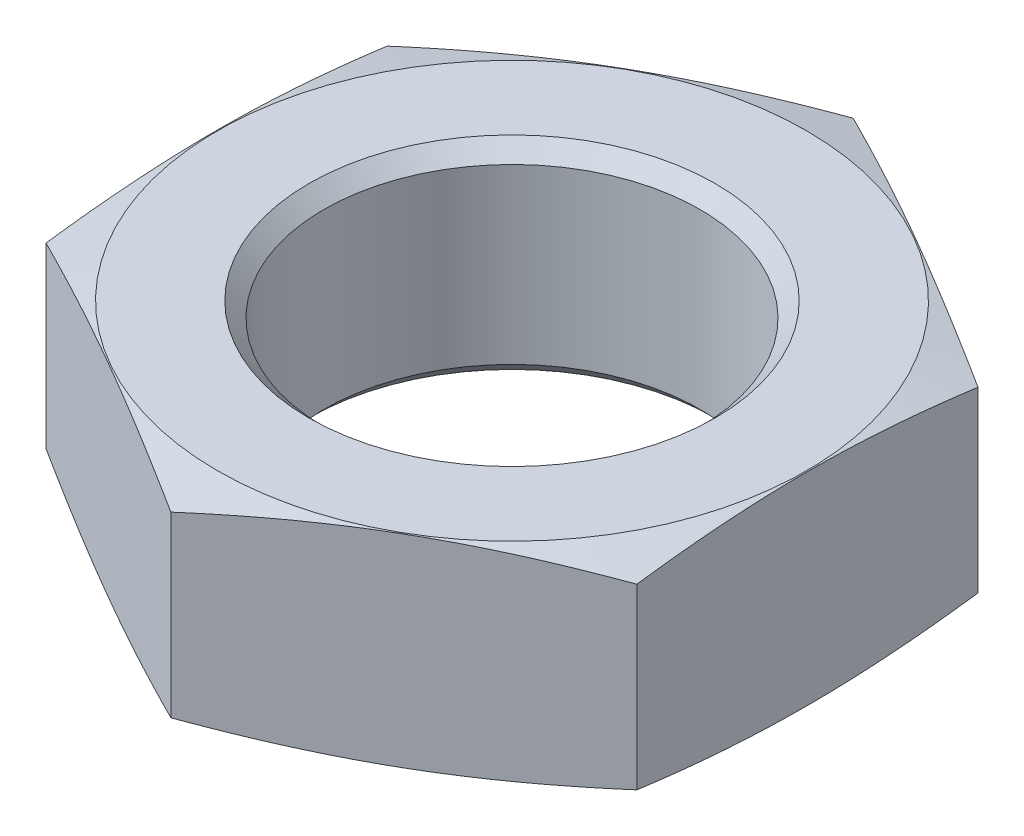
SolidWorks part; units mm, degrees
ref_plane "Ebene vorne" through (0, 0, 0) normal (0, 0, 1) x (1, 0, 0)
ref_plane "Ebene oben" through (0, 0, 0) normal (0, 1, 0) x (1, 0, 0)
ref_plane "Ebene rechts" through (0, 0, 0) normal (1, 0, 0) x (0, 0, -1)
sketch "Skizze1" plane through (0, 0, 0) normal (0, 0, 1) x (1, 0, 0)
  line L0 (0, 0) -> (15.95, 0)
  line L1 (15.95, 0) -> (36.4763, -5.5)
  line L2 (36.4763, -5.5) -> (15.95, -11)
  line L3 (15.95, -11) -> (0, -11)
  line L4 (0, -11) -> (0, 0)
  line L5 (0, -11) -> (0, 0) construction
revolve "Rotation1" add sketch "Skizze1" angle 360 about L5
sketch "Skizze2" plane through (0, 0, 0) normal (0, 1, 0) x (1, 0, 0)
  line L0 (-64, 64) -> (-64, -64)
  line L1 (-64, -64) -> (64, -64)
  line L2 (64, -64) -> (64, 64)
  line L3 (64, 64) -> (-64, 64)
  line L4 (-16, -9.2376) -> (0, -18.4752)
  line L5 (0, -18.4752) -> (16, -9.2376)
  line L6 (16, -9.2376) -> (16, 9.2376)
  line L7 (16, 9.2376) -> (0, 18.4752)
  line L8 (0, 18.4752) -> (-16, 9.2376)
  line L9 (-16, 9.2376) -> (-16, -9.2376)
extrude "Schnitt-Linear austragen1" cut sketch "Skizze2" along normal blind 12 and the other way blind 12
sketch "Skizze3" plane through (0, 0, 0) normal (0, 0, 1) x (1, 0, 0)
  line L0 (0, 0) -> (11, 0)
  line L1 (11, 0) -> (10.188, -0.812)
  line L2 (10.188, -0.812) -> (10.188, -10.188)
  line L3 (10.188, -10.188) -> (11, -11)
  line L4 (11, -11) -> (0, -11)
  line L5 (0, -11) -> (0, 0)
  line L6 (0, -11) -> (0, 0) construction
revolve "Schnitt-Rotation1" cut sketch "Skizze3" angle 360 about L6 reverse direction yes
cosmetic thread "Gewindedarstellung1" parameters "D1"=11, "D2"=22
ref_plane "Ebene1" through (0, -5.5, 0) normal (0, 1, 0) x (1, 0, 0)
ref_plane "2CYL XY" through (0, -5.5, 0) normal (0, 1, 0) x (1, 0, 0)
ref_plane "2CYL XZ" through (0, 0, 0) normal (0, 0, 1) x (1, 0, 0)
ref_plane "2CYL YZ" through (0, 0, 0) normal (1, 0, 0) x (0, 0, -1)
ref_axis "2CYL X" through (-80.9, -5.5, 0) along (1, 0, 0)
ref_axis "2CYL Y" through (0, -5.5, 50) along (0, 0, -1)
ref_axis "2CYL Z" through (0, 50, 0) along (0, -1, 0)
sketch3d "2CYL"
  point P0 (0, -5.5, 0)
ref_plane "din439b_punkt XY" through (0, 0, 0) normal (0, 1, 0) x (1, 0, 0)
ref_plane "din439b_punkt XZ" through (0, 0, 0) normal (0, 0, 1) x (1, 0, 0)
ref_plane "din439b_punkt YZ" through (0, 0, 0) normal (1, 0, 0) x (0, 0, -1)
ref_axis "din439b_punkt X" through (-80.9, 0, 0) along (1, 0, 0)
ref_axis "din439b_punkt Y" through (0, 0, 50) along (0, 0, -1)
ref_axis "din439b_punkt Z" through (0, 50, 0) along (0, -1, 0)
sketch3d "din439b_punkt"
  point P0 (0, 0, 0)
